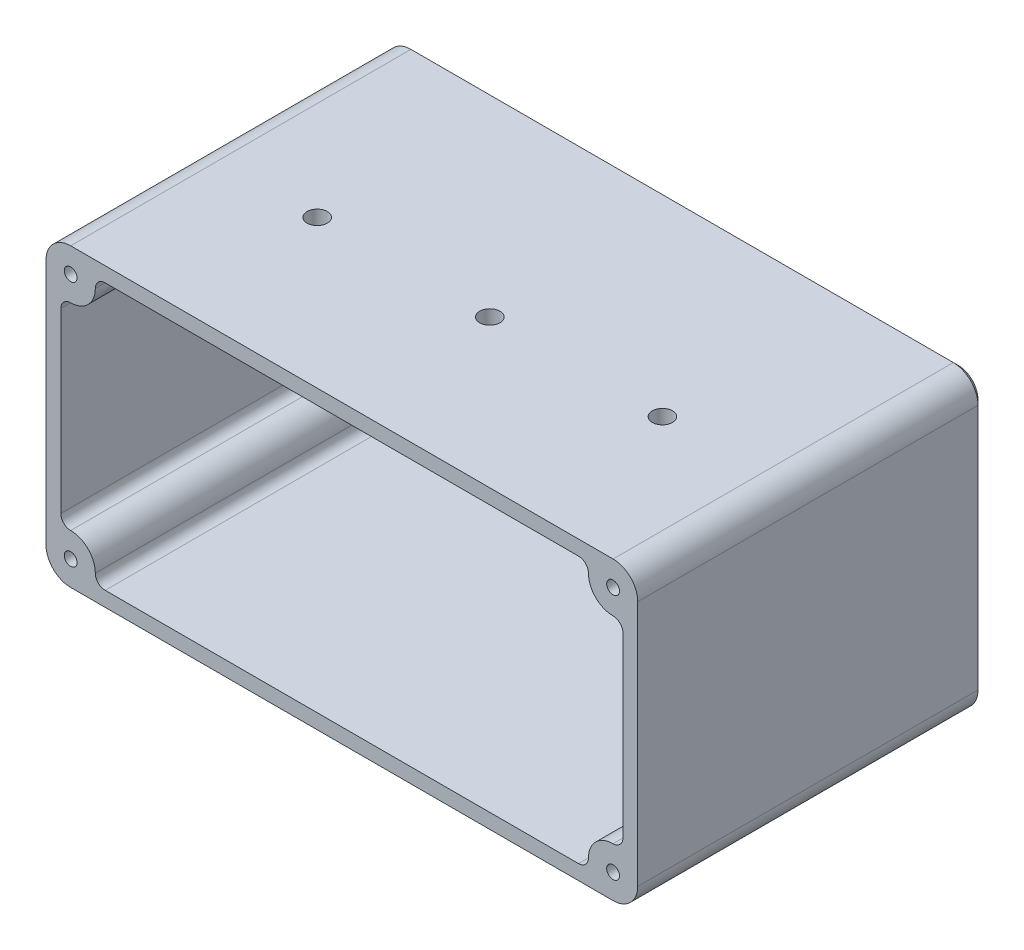
SolidWorks part; units mm, degrees
ref_plane "Front Plane" through (0, 0, 0) normal (0, 0, 1) x (1, 0, 0)
ref_plane "Top Plane" through (0, 0, 0) normal (0, 1, 0) x (1, 0, 0)
ref_plane "Right Plane" through (0, 0, 0) normal (1, 0, 0) x (0, 0, -1)
sketch "Sketch1" plane through (0, 0, 0) normal (0, 0, 1) x (1, 0, 0)
  line L1 (-60, 30) -> (60, 30)
  line L2 (-60, 30) -> (-60, -30)
  line L3 (-60, -30) -> (60, -30)
  line L4 (60, 30) -> (60, -30)
  line L5 (-60, 30) -> (60, -30) construction
  line L6 (-60, -30) -> (60, 30) construction
  point P0 (0, 0)
  dimension "D1" = 120
  dimension "D2" = 60
extrude "Boss-Extrude1" add sketch "Sketch1" along normal blind 70
sketch "Sketch2" plane through (0, 0, 70) normal (0, 0, 1) x (1, 0, 0)
  line L0 (60, 30) -> (-60, 30) construction
  line L1 (-57, 27) -> (57, 27)
  line L2 (-57, 27) -> (-57, -27)
  line L3 (-57, -27) -> (57, -27)
  line L4 (57, 27) -> (57, -27)
  line L5 (-57, 27) -> (57, -27) construction
  line L6 (-57, -27) -> (57, 27) construction
  line L7 (60, -30) -> (60, 30) construction
  point P0 (0, 0)
  dimension "D1" = 3
  dimension "D2" = 3
extrude "Cut-Extrude1" cut sketch "Sketch2" against normal offset from surface (67 mm away) 3 up to face at (0, 0, 0)
fillet "Fillet3" radius 5 4 edges at (-60, -30, 35) (60, -30, 35) (60, 30, 35) (-60, 30, 35)
fillet "Fillet4" radius 2 4 edges at (57, 27, 36.5) (57, -27, 36.5) (-57, -27, 36.5) (-57, 27, 36.5)
sketch "Sketch4" plane through (0, 0, 70) normal (0, 0, 1) x (1, 0, 0)
  line L0 (55, 30) -> (-55, 30) construction
  line L1 (0, -33) -> (0, 33) construction
  line L2 (44, 0) -> (-44, 0) construction
  circle A0 centre (-55, 25) radius 5
  circle A1 centre (55, 25) radius 5
  circle A2 centre (55, -25) radius 5
  circle A3 centre (-55, -25) radius 5
extrude "Boss-Extrude3" add sketch "Sketch4" against normal up to surface (67 mm away) up to face at (0, 0, 3)
fillet "Fillet5" radius 2 8 edges at (-57, -20.4174, 36.5) (-50.4174, -27, 36.5) (50.4174, -27, 36.5) (57, -20.4174, 36.5) (57, 20.4174, 36.5) (50.4174, 27, 36.5) (-57, 20.4174, 36.5) (-50.4174, 27, 36.5)
sketch "Sketch5" plane through (0, 0, 70) normal (0, 0, 1) x (1, 0, 0)
  circle A0 centre (-55, 25) radius 1.3
  circle A1 centre (55, 25) radius 1.3
  circle A2 centre (55, -25) radius 1.3
  circle A3 centre (-55, -25) radius 1.3
  dimension "D1" = 2.6
extrude "Cut-Extrude2" cut sketch "Sketch5" against normal blind 18
sketch "Sketch6" plane through (0, 30, 0) normal (0, 1, 0) x (1, 0, 0)
  circle A0 centre (0, -40) radius 2.05
  circle A1 centre (35, -40) radius 2.05
  circle A2 centre (-35, -40) radius 2.05
  dimension "D4" = 4.1
  dimension "D1" = 40
  dimension "D2" = 70
  dimension "D3" = 35
extrude "Cut-Extrude3" cut sketch "Sketch6" against normal blind 3
chamfer "Chamfer2" distance 1 angle 45 8 edges at (0, 30, 0) (-58.5355, 28.5355, 0) (58.5355, 28.5355, 0) (-60, 0, 0) (60, 0, 0) (-58.5355, -28.5355, 0) (58.5355, -28.5355, 0) (0, -30, 0)
sketch "Sketch7" plane through (0, 0, 0) normal (0, 0, -1) x (-1, 0, 0)
  circle A0 centre (-43, 18) radius 6.25
  dimension "D1" = 12.5
  dimension "D2" = 43
  dimension "D3" = 18
extrude "Cut-Extrude4" cut sketch "Sketch7" against normal through all
sketch "Sketch8" plane through (0, 0, 3) normal (0, 0, 1) x (1, 0, 0)
  circle A0 centre (43, 18) radius 8.75
  dimension "D1" = 17.5
extrude "Cut-Extrude5" cut sketch "Sketch8" against normal blind 1.5
